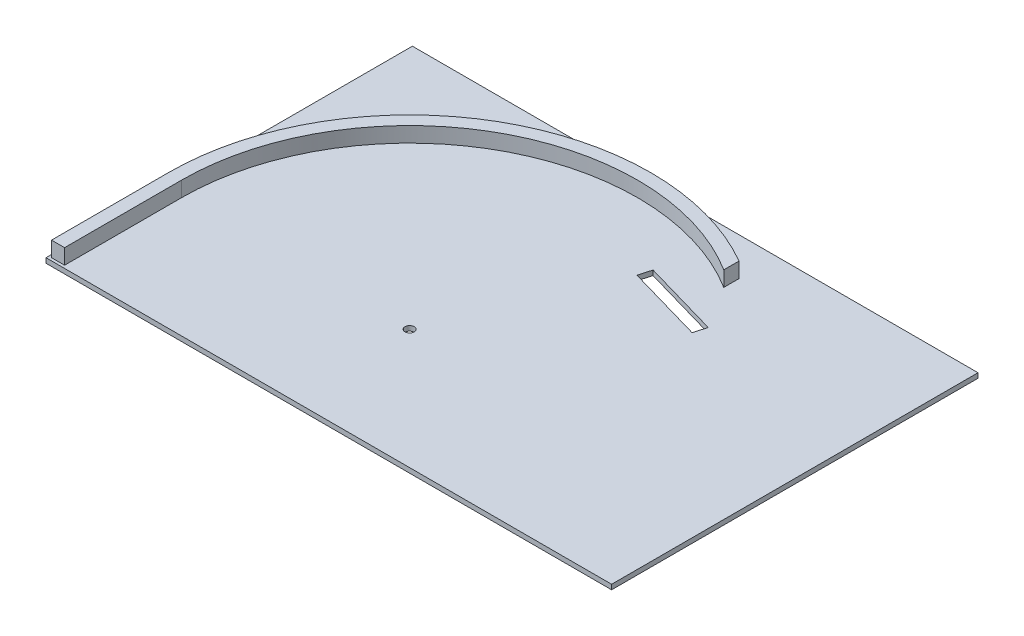
SolidWorks part; units mm, degrees
material "Particle Board"
ref_plane "Front Plane" through (0, 0, 0) normal (0, 0, 1) x (1, 0, 0)
ref_plane "Top Plane" through (0, 0, 0) normal (0, 1, 0) x (1, 0, 0)
ref_plane "Right Plane" through (0, 0, 0) normal (1, 0, 0) x (0, 0, -1)
sketch "Sketch3" plane through (0, 0, 0) normal (0, 1, 0) x (1, 0, 0)
  line L1 (0, 0) -> (-839.8654, 0) construction
  line L2 (0, 0) -> (-451.1992, 260.5) construction
  line L5 (-524, 0) -> (-554, 0)
  line L6 (277.6777, 444.3772) -> (277.6777, 479.3862)
  circle A0 centre (0, 0) radius 254 construction
  arc A3 (277.6777, 444.3772) -> (-524, 0) centre (0, 0) ccw
  arc A4 (277.6777, 479.3862) -> (-554, 0) centre (0, 0) ccw
  arc A5 (293.5753, 469.8186) -> (-554, 0) centre (0, 0) ccw construction
  dimension "D1" = 524
  dimension "D2" = 30
  dimension "D4" = 122
  dimension "D5" = 508
  dimension "D3" = 30
extrude "Boss-Extrude1" add sketch "Sketch3" along normal blind 35
sketch "Sketch4" plane through (0, 0, 0) normal (0, 1, 0) x (1, 0, 0)
  line L0 (-538.2597, 554) -> (609.3192, 554) construction
  line L5 (-560.35, 566.7) -> (739.65, 566.7)
  line L6 (-560.35, 566.7) -> (-560.35, -275.4)
  line L7 (-560.35, -275.4) -> (739.65, -275.4)
  line L8 (739.65, 566.7) -> (739.65, -275.4)
  arc A0 (277.6777, 479.3862) -> (-554, 0) centre (0, 0) ccw construction
  dimension "D1" = 275.4
  dimension "D2" = 6.35
  dimension "D3" = 12.7
  dimension "D4" = 1300
extrude "Boss-Extrude2" add sketch "Sketch4" against normal blind 11.1125
hole_wizard "Ø20.0mm Dowel Hole1" positions "Sketch6" profile "Sketch7" hole size "Ø20.0" standard "ANSI Metric" end condition through all
sketch "Sketch6" plane through (0, 0, 0) normal (0, 1, 0) x (1, 0, 0)
  point P0 (0, 0)
sketch "Sketch7" plane through (0, 0, 0) normal (1, 0, 0) x (0, 0, 1)
  line L0 (0, 0) -> (0, 11.1125)
  line L1 (0, 11.1125) -> (10.5, 11.1125)
  line L2 (10.5, 11.1125) -> (10.5, 0)
  line L5 (10.5, 0) -> (0, 0)
  line L11 (0, -6.35) -> (0, 107.95) construction
  dimension "Thru Hole Dia." = 21
  dimension "Thru Hole Depth" = 11.1125
ref_plane "Plane1" through (0, 0, 269.05) normal (0, 0, 1) x (1, 0, 0)
sketch "Sketch8" plane through (0, 0, 0) normal (0, 0, 1) x (1, 0, 0)
  line L1 (-554, 35) -> (-524, 35)
  line L2 (-554, 35) -> (-554, 0)
  line L3 (-554, 0) -> (-524, 0)
  line L4 (-524, 35) -> (-524, 0)
extrude "Boss-Extrude3" add sketch "Sketch8" along normal up to surface (269.05 mm away) up to plane "Plane1"
sketch "Sketch9" plane through (0, 0, 0) normal (0, 1, 0) x (1, 0, 0)
  line L0 (339.65, 346.7) -> (161.8166, 397.6929)
  line L1 (161.8166, 397.6929) -> (153.5475, 368.8551)
  line L2 (153.5475, 368.8551) -> (331.3809, 317.8621)
  line L3 (331.3809, 317.8621) -> (339.65, 346.7)
  line L4 (739.65, 566.7) -> (-560.35, 566.7) construction
  line L5 (739.65, -275.4) -> (739.65, 566.7) construction
  dimension "D1" = 185
  dimension "D2" = 30
  dimension "D3" = 16
  dimension "D4" = 400
  dimension "D5" = 220
extrude "Cut-Extrude1" cut sketch "Sketch9" against normal through all
